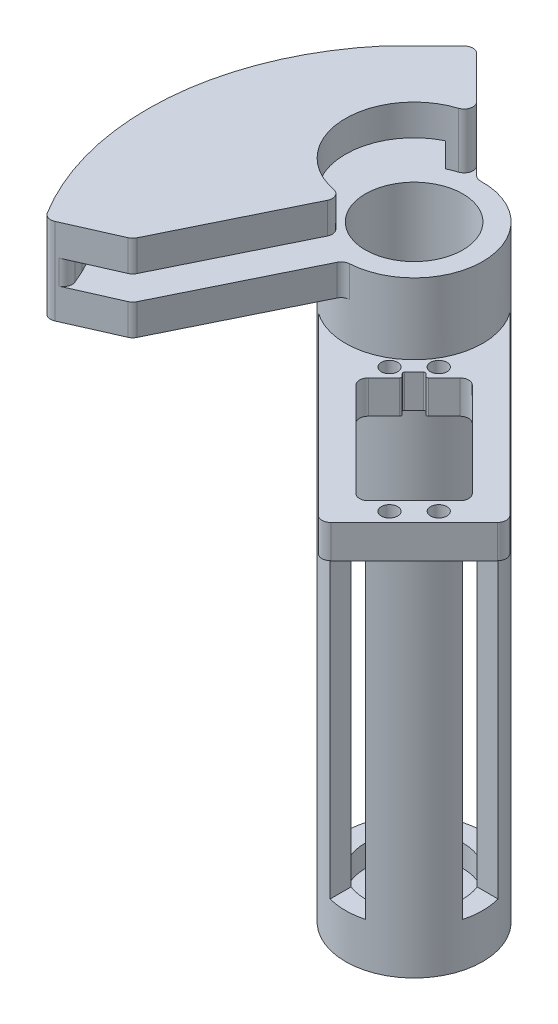
SolidWorks part; units mm, degrees
note: The reader was unsure of these and kept them because the rebuilt part matched: shared geometry of "Sketch25<3>".
ref_plane "Front Plane" through (0, 0, 0) normal (0, 0, 1) x (1, 0, 0)
ref_plane "Top Plane" through (0, 0, 0) normal (0, 1, 0) x (1, 0, 0)
ref_plane "Right Plane" through (0, 0, 0) normal (1, 0, 0) x (0, 0, -1)
sketch "Sketch1" plane through (0, 0, 0) normal (0, 1, 0) x (1, 0, 0)
  circle A0 centre (0, 0) radius 13.97
  circle A1 centre (0, 0) radius 19.685
  dimension "D1" = 27.94
  dimension "D2" = 39.37
extrude "Boss-Extrude1" add sketch "Sketch1" along normal blind 173.99
sketch "Sketch2" plane through (0, 0, 0) normal (0, -1, 0) x (1, 0, 0)
  circle A0 centre (0, 0) radius 13.97
extrude "Boss-Extrude2" add sketch "Sketch2" against normal blind 6.35
ref_plane "Plane1" through (0, 0, 16.51) normal (0, 0, 1) x (1, 0, 0)
sketch "Sketch5" plane through (0, 0, 0) normal (1, 0, 0) x (0, 0, -1)
  line L0 (55, 0) -> (-55, 0) construction
  line L1 (5.08, 12.7) -> (-5.08, 12.7)
  line L2 (5.08, 12.7) -> (5.08, 161.29)
  line L3 (5.08, 161.29) -> (-5.08, 161.29)
  line L4 (-5.08, 12.7) -> (-5.08, 161.29)
  line L5 (19.685, 173.99) -> (-19.685, 173.99) construction
  line L6 (0, 0) -> (0, 12.7) construction
  line L7 (-5.08, 114.3) -> (7.62, 114.3)
  line L8 (-5.08, 88.9) -> (7.62, 88.9)
  line L9 (-5.08, 165.1) -> (5.08, 165.1)
  line L10 (-5.08, 190.5) -> (5.08, 190.5)
  dimension "D1" = 12.7
  dimension "D2" = 12.7
  dimension "D3" = 10.16
  dimension "D4" = 12.7
  dimension "D5" = 12.7
  dimension "D6" = 76.2
  dimension "D7" = 25.4
  dimension "D8" = 25.4
  dimension "D9" = 50.8
sketch "Sketch8" plane through (0, 0, 0) normal (0, 0, 1) x (1, 0, 0)
  line L0 (-19.685, 0) -> (19.685, 0) construction
  line L1 (5.08, 12.7) -> (-5.08, 12.7)
  line L2 (5.08, 12.7) -> (5.08, 161.29)
  line L3 (5.08, 161.29) -> (-5.08, 161.29)
  line L4 (-5.08, 12.7) -> (-5.08, 161.29)
  line L5 (19.685, 173.99) -> (-19.685, 173.99) construction
  line L6 (0, 12.7) -> (0, 0) construction
  line L7 (5.08, 88.9) -> (-5.08, 88.9)
  line L8 (5.08, 114.3) -> (-5.08, 114.3)
  line L9 (5.08, 165.1) -> (-5.08, 165.1)
  line L10 (5.08, 190.5) -> (-5.08, 190.5)
  dimension "D1" = 12.7
  dimension "D2" = 10.16
  dimension "D3" = 12.7
  dimension "D4" = 76.2
  dimension "D5" = 25.4
  dimension "D6" = 25.4
  dimension "D7" = 50.8
sketch "Sketch7" plane through (0, 6.35, 0) normal (0, 1, 0) x (1, 0, 0)
  circle A0 centre (0, 0) radius 6.35
extrude "Cut-Extrude4" cut sketch "Sketch7" against normal through all
ref_plane "Plane5" through (0, 0, 0) normal (0.7071, 0, 0.7071) x (0.7071, 0, -0.7071)
ref_plane "Plane6" through (13.9194, 0, 13.9194) normal (0.7071, 0, 0.7071) x (0.7071, 0, -0.7071)
sketch "Sketch9" plane through (13.9194, 0, 13.9194) normal (0.7071, 0, 0.7071) x (0.7071, 0, -0.7071)
  line L0 (-19.431, 153.642) -> (19.431, 153.642)
  line L1 (-19.431, 153.642) -> (-19.431, 144.117)
  line L2 (19.431, 153.642) -> (19.431, 144.117)
  line L3 (-19.431, 144.117) -> (19.431, 144.117)
  line L5 (0, 153.642) -> (0, 0) construction
  line L8 (9.5, 153.642) -> (-9.5, 153.642) construction
  dimension "D1" = 38.862
  dimension "D2" = 9.525
extrude "Boss-Extrude3" add sketch "Sketch9" along normal blind 6.35 and the other way up to next
sketch "Sketch10" plane through (18.4095, 0, 18.4095) normal (0.7071, 0, 0.7071) x (0.7071, 0, -0.7071)
  line L0 (-19.431, 153.642) -> (-19.431, 144.117)
  line L1 (-19.431, 153.642) -> (-11.811, 153.642)
  line L2 (-19.431, 144.117) -> (-11.811, 144.117)
  line L3 (-11.811, 153.642) -> (-11.811, 144.117)
  line L4 (19.431, 144.117) -> (19.431, 153.642)
  line L5 (19.431, 144.117) -> (11.811, 144.117)
  line L6 (19.431, 153.642) -> (11.811, 153.642)
  line L7 (11.811, 144.117) -> (11.811, 153.642)
  dimension "D1" = 7.62
  dimension "D2" = 7.62
extrude "Boss-Extrude4" add sketch "Sketch10" along normal blind 50.8
sketch "Sketch11" plane through (-8.3516, 0, 8.3516) normal (0.7071, 0, -0.7071) x (-0.7071, 0, -0.7071)
  line L0 (-76.835, 144.117) -> (-76.835, 153.642) construction
  line L1 (-76.835, 153.642) -> (-76.835, 144.117)
  line L2 (-76.835, 153.642) -> (-69.215, 153.642)
  line L3 (-76.835, 144.117) -> (-69.215, 144.117)
  line L4 (-69.215, 153.642) -> (-69.215, 144.117)
  point P0 (-69.215, 148.8795)
  point P1 (-76.835, 148.8795)
  dimension "D1" = 7.62
extrude "Boss-Extrude5" add sketch "Sketch11" along normal up to next
fillet "Fillet1" radius 2.54 6 edges at (40.5908, 148.8795, 68.0703) (68.0703, 148.8795, 40.5908) (26.7612, 148.8795, 10.0579) (57.294, 148.8795, 40.5908) (10.0579, 148.8795, 26.7612) (40.5908, 148.8795, 57.294)
sketch "Sketch12" plane through (0, 153.642, 0) normal (0, 1, 0) x (1, 0, 0)
  circle A0 centre (48.0338, -55.1048) radius 2.3559
  circle A1 centre (55.1048, -48.0338) radius 2.3559
  circle A2 centre (19.2545, -12.1834) radius 2.3558
  circle A3 centre (12.1834, -19.2545) radius 2.3558
  dimension "D1" = 4.7117
extrude "Cut-Extrude7" cut sketch "Sketch12" against normal up to next
sketch "Sketch22" plane through (0, 153.642, 0) normal (0, 1, 0) x (1, 0, 0)
  line L0 (16.7033, -20.1158) -> (20.1158, -16.7033)
  line L1 (16.7033, -20.1158) -> (15.2664, -18.6789)
  line L2 (20.1158, -16.7033) -> (18.6789, -15.2664)
  line L3 (15.2664, -18.6789) -> (18.6789, -15.2664)
  line L4 (24.9651, -11.8539) -> (11.8539, -24.9651) construction
  point P6 (18.4095, -18.4095)
  dimension "D1" = 4.826
  dimension "D2" = 2.032
extrude "Cut-Extrude9" cut sketch "Sketch22" against normal up to next
fillet "Fillet5" radius 0.508 4 edges at (16.7033, 148.8795, 20.1158) (15.2664, 148.8795, 18.6789) (18.6789, 148.8795, 15.2664) (20.1158, 148.8795, 16.7033)
sketch "Sketch24" plane through (0, 173.99, 0) normal (0, 1, 0) x (1, 0, 0)
  line L0 (-1.6548, 19.6153) -> (-18.8585, 36.8191)
  line L1 (-37.7855, -68.1464) -> (-20.3622, -60.4437)
  line L2 (-18.8585, 36.8191) -> (-32.3289, 23.3487)
  line L3 (42.3868, -66.2743) -> (66.2743, -42.3868) construction
  line L8 (-20.3622, -60.4437) -> (-0.3489, -19.6819)
  circle A0 centre (0, 0) radius 19.685 construction
  arc A1 (-32.3289, 23.3487) -> (-37.7855, -68.1464) centre (26.0427, -26.0427) ccw
  circle A3 centre (0, 0) radius 19.685
  arc A4 (-1.6548, 19.6153) -> (-0.3489, -19.6819) centre (0, 0) ccw
  dimension "D1" = 12.7
  dimension "D2" = 19.05
  dimension "D3" = 76.2
  dimension "D5" = 140
  dimension "D6" = 19.05
  dimension "D7" = 0
extrude "Boss-Extrude6" add sketch "Sketch24" against normal blind 8.89 and the other way blind 15.875
sketch "Sketch25" plane through (0, 173.99, 0) normal (0, 1, 0) x (1, 0, 0)
  line L0 (-37.7855, -68.1464) -> (-20.3622, -60.4437) construction
  line L1 (-35.2531, -60.084) -> (-32.6855, -65.8918)
  line L3 (-1.6548, 19.6153) -> (-18.8585, 36.8191) construction
  line L4 (-18.8585, 36.8191) -> (-32.3289, 23.3487) construction
  line L5 (-1.6548, 19.6153) -> (-18.8585, 36.8191)
  line L6 (-18.8585, 36.8191) -> (-32.3289, 23.3487)
  line L7 (-37.7855, -68.1464) -> (-20.3622, -60.4437)
  line L8 (-6.1449, 15.1252) -> (-18.8585, 27.8388)
  line L9 (-18.8585, 27.8388) -> (-27.648, 19.0494)
  line L10 (-35.2531, -60.084) -> (-22.9298, -54.636)
  line L11 (-20.3622, -60.4437) -> (-0.3489, -19.6819) construction
  line L12 (-20.3622, -60.4437) -> (-0.3489, -19.6819)
  line L13 (-22.9298, -54.636) -> (-16.0083, -51.5761)
  arc A0 (-32.3289, 23.3487) -> (-37.7855, -68.1464) centre (26.0427, -26.0427) ccw construction
  arc A1 (-32.3289, 23.3487) -> (-37.7855, -68.1464) centre (26.0427, -26.0427) ccw
  arc A2 (-27.648, 19.0494) -> (-35.2531, -60.084) centre (26.0427, -26.0427) ccw
  arc A3 (-1.6548, 19.6153) -> (-0.3489, -19.6819) centre (0, 0) ccw construction
  arc A4 (-1.6548, 19.6153) -> (-0.3489, -19.6819) centre (0, 0) ccw
  arc M1 (-1.6548, 19.6153) -> (-0.3489, -19.6819) centre (0, 0) ccw
  dimension "D1" = 6.35
extrude "Cut-Extrude10" cut sketch "Sketch25" along normal blind 6.985 contours L9 A2 L10 L13 L12 L8 M1
extrude "Cut-Extrude11" cut sketch "Sketch25<3>" along normal blind 6.985 contours L13 L10 L1 L7 L12
sketch "Sketch25<3>" plane through (0, 173.99, 0) normal (0, 1, 0) x (1, 0, 0) same geometry as "Sketch25"
fillet "Fillet7" radius 2.54 7 edges at (-0.3489, 169.545, 19.6819) (-0.3489, 185.42, 19.6819) (-20.3622, 169.545, 60.4437) (-20.3622, 185.42, 60.4437) (-37.7855, 177.4825, 68.1464) (-32.6855, 177.4825, 65.8918) (-18.8585, 177.4825, -27.8388)
fillet "Fillet8" radius 2.54 2 edges at (-18.8585, 177.4825, -36.8191) (-1.6548, 181.9275, -19.6153)
fillet "Fillet9" radius 2.54 1 edges at (-1.6548, 169.545, -19.6153)
extrude "Cut-Extrude12" cut sketch "Sketch5" against normal through all both and the other way through all contours L4 L8 L2 L7 | L8 L4 L1 L2
extrude "Cut-Extrude13" cut sketch "Sketch8" against normal through all both and the other way through all contours L2 L8 L4 L7 | L2 L7 L4 L1
